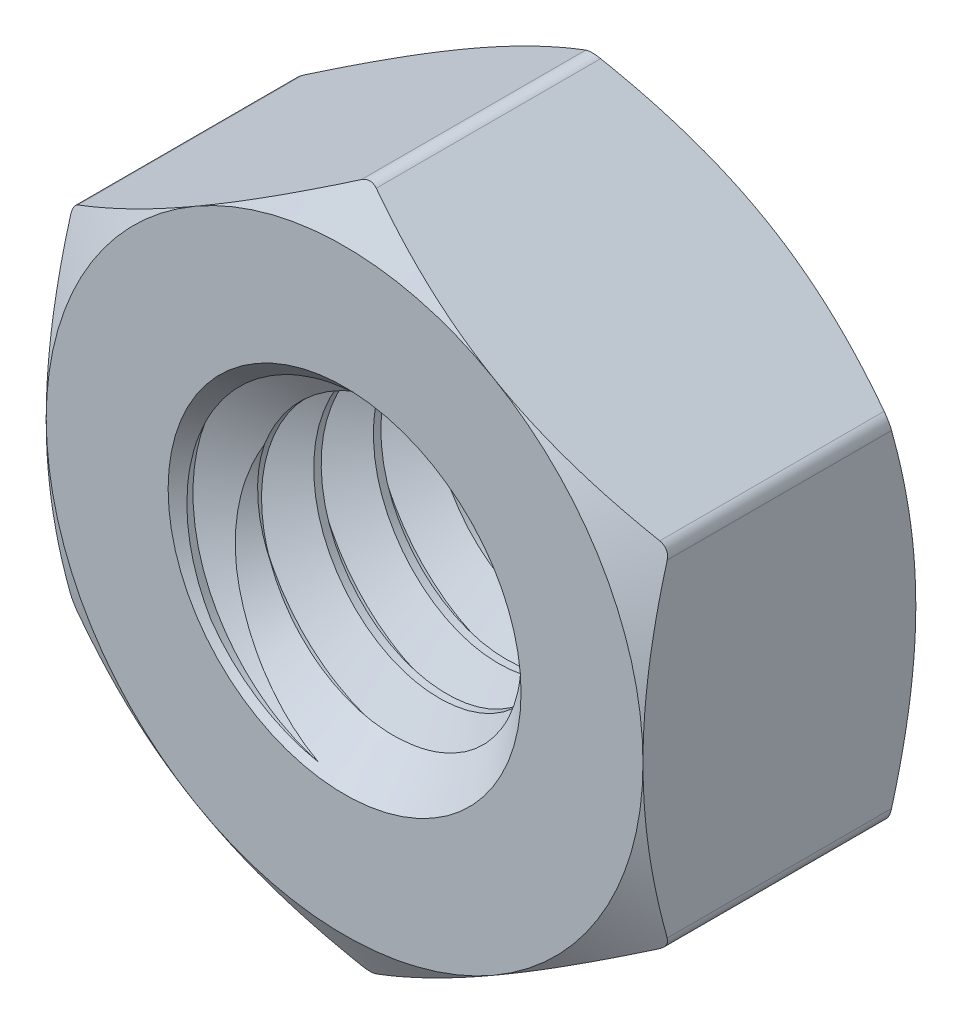
SolidWorks part; units mm, degrees
ref_plane "Front" through (0, 0, 0) normal (0, 0, 1) x (1, 0, 0)
ref_plane "Top" through (0, 0, 0) normal (0, 1, 0) x (1, 0, 0)
ref_plane "Right" through (0, 0, 0) normal (1, 0, 0) x (0, 0, -1)
sketch "Sketch1" plane through (0, 0, 0) normal (0, 0, 1) x (1, 0, 0)
  line L0 (0, 2) -> (0, 1.3) construction
  line L1 (-3.5, 2.0207) -> (-3.5, -2.0207)
  line L2 (-3.5, -2.0207) -> (0, -4.0415)
  line L3 (0, -4.0415) -> (3.5, -2.0207)
  line L4 (3.5, -2.0207) -> (3.5, 2.0207)
  line L5 (3.5, 2.0207) -> (0, 4.0415)
  line L6 (0, 4.0415) -> (-3.5, 2.0207)
  circle A0 centre (0, 0) radius 3.5 construction
  circle A1 centre (0, 0) radius 2 construction
  point P10 (0, 2)
  dimension "Width" = 7
  dimension "Thread Size" = 4
  dimension "Thread Pitch" = 0.7
sketch "Sketch2" plane through (0, 0, 0) normal (1, 0, 0) x (0, 0, -1)
  line L0 (-1.6, 0) -> (1.6, 0) construction
  line L1 (-1.6, 4.0415) -> (1.6, 4.0415) construction
  dimension "Height" = 3.2
sketch "Sketch15" plane through (0, 0, 0) normal (0, 0, 1) x (1, 0, 0)
  line L1 (0, 4.0415) -> (-3.5, 2.0207)
  line L2 (-3.5, 2.0207) -> (-3.5, -2.0207)
  line L3 (-3.5, -2.0207) -> (0, -4.0415)
  line L4 (0, -4.0415) -> (3.5, -2.0207)
  line L5 (3.5, -2.0207) -> (3.5, 2.0207)
  line L6 (3.5, 2.0207) -> (0, 4.0415)
  circle A0 centre (0, 0) radius 3.5 construction
extrude "Boss-Extrude2" add sketch "Sketch15" along normal mid plane 3.2
sketch "Sketch16" plane through (0, 0, 0) normal (0, 0, 1) x (1, 0, 0)
  circle A0 centre (0, 0) radius 2 construction
  circle A1 centre (0, 0) radius 2
sketch "Sketch4" plane through (0, 0, -1.6) normal (0, 0, -1) x (-1, 0, 0)
  circle A0 centre (0, 0) radius 2 construction
  circle A1 centre (0, 0) radius 2
extrude "Cut-Extrude4" cut sketch "Sketch16" against normal through all both and the other way through all
sketch "Sketch7" plane through (0, 0, 1.6) normal (0, 0, 1) x (1, 0, 0)
  circle A0 centre (0, 0) radius 3.5 construction
  circle A1 centre (0, 0) radius 3.5
extrude "Cut-Extrude5" cut sketch "Sketch7" against normal through all draft 60 flip side to cut
mirror "Mirror4" about plane through (0, 0, 0) normal (0, 0, 1) of "Cut-Extrude5"
fillet "Fillet2" radius 0.175 6 edges at (-3.5, 2.0207, 0) (-3.5, -2.0207, 0) (0, -4.0415, 0) (3.5, -2.0207, 0) (3.5, 2.0207, 0) (0, 4.0415, 0)
sketch "Sketch8" plane through (0, 0, 1.6) normal (0, 0, 1) x (1, 0, 0)
  line L0 (0.5176, -1.9319) -> (0, 0) construction
  line L2 (0, 2) -> (0, 1.3) construction
  circle A0 centre (0, 0) radius 2 construction
  point P0 (0.5176, -1.9319)
  dimension "D1" = 15
sketch "Sketch13" plane through (0, 0, -1.6) normal (0, 0, -1) x (-1, 0, 0)
  circle A0 centre (0, 0) radius 2 construction
  circle A1 centre (0, 0) radius 2
extrude "Boss-Extrude1" add sketch "Sketch13" against normal up to surface (3.2 mm away) separate body up to face at (2, 0, 1.6)
curve "Helix/Spiral3" pitch 0.7 height 4.6 radius 2 centre (0, 0, -1.6) axis (0, 0, 1) start towards (0, 1, 0)
sketch "Sketch12" plane through (0, 0, 0) normal (1, 0, 0) x (0, 0, -1)
  line L0 (2.2125, 2) -> (1.6, 2)
  line L1 (2.2125, 2) -> (1.95, 1.5453)
  line L2 (1.95, 1.5453) -> (1.8625, 1.5453)
  line L3 (1.8625, 1.5453) -> (1.6, 2)
  line L4 (1.9063, 1.5453) -> (1.9063, 2) construction
  line L5 (1.7313, 1.7727) -> (2.0813, 1.7727) construction
  dimension "D1" = 60
  dimension "D2" = 0.0875
  dimension "D3" = 0.35
sweep "Cut-Sweep1" cut profiles "Sketch12" path "Helix/Spiral3" align with end faces yes
sketch "Sketch17" plane through (0, 0, 1.6) normal (0, 0, 1) x (1, 0, 0)
  circle A1 centre (0, 0) radius 2
  circle A2 centre (0, 0) radius 2
  dimension "D1" = 0
extrude "Boss-Extrude3" add sketch "Sketch17" against normal up to surface (3.2 mm away) up to face at (2, 0, -1.6)
combine bodies "Combine1" operation type subtract main body 127 bodies to subtract 118
sketch "Sketch10" plane through (0, 0, 1.6) normal (0, 0, 1) x (1, 0, 0)
  circle A0 centre (0, 0) radius 2 construction
  circle A1 centre (0, 0) radius 2 construction
  circle A2 centre (0, 0) radius 2.07
  dimension "D1" = 0.07
extrude "Cut-Extrude2" cut sketch "Sketch10" against normal through all draft 45
sketch "Sketch11" plane through (0, 0, -1.6) normal (0, 0, -1) x (-1, 0, 0)
  circle A1 centre (0, 0) radius 2.07 construction
  circle A2 centre (0, 0) radius 2.07
extrude "Cut-Extrude3" cut sketch "Sketch11" against normal through all draft 45
equation "\"D1\"= \"Height@Sketch2\""
equation "\"D3@Helix/Spiral3\"=\"Height@Sketch2\"+\"Thread Pitch@Sketch1\"*2"
equation "\"D4@Helix/Spiral3\"=\"Thread Pitch@Sketch1\""
equation "\"D2@Sketch12\" = \"D4@Helix/Spiral3\"*.125"
equation "\"D3@Sketch12\" = \"D4@Helix/Spiral3\"*.50"
equation "\"D1@Boss-Extrude2\"=\"Height@Sketch2\""
equation "\"D1@Fillet2\"=\"Width@Sketch1\"*0.025"
equation "\"D1@Sketch10\"=\"Thread Pitch@Sketch1\"*0.1"
